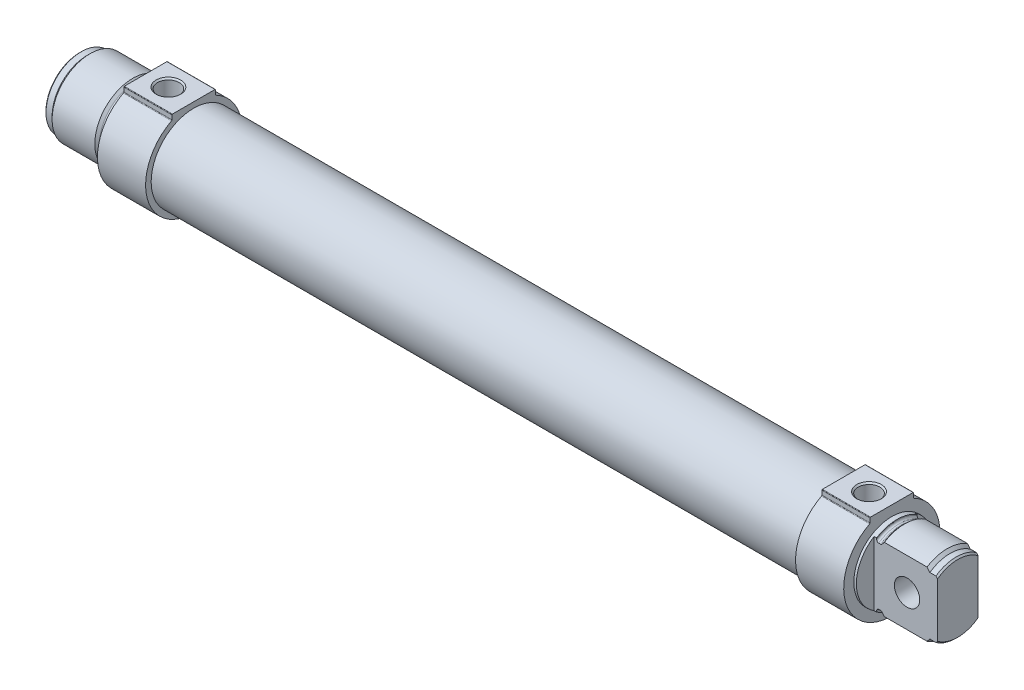
SolidWorks part; units mm, degrees
ref_plane "Front Plane" through (0, 0, 0) normal (0, 0, 1) x (1, 0, 0)
ref_plane "Top Plane" through (0, 0, 0) normal (0, 1, 0) x (1, 0, 0)
ref_plane "Right Plane" through (0, 0, 0) normal (1, 0, 0) x (0, 0, -1)
sketch "Sketch1" plane through (0, 0, 0) normal (0, 0, 1) x (1, 0, 0)
  line L0 (0, 0) -> (0, 13.3)
  line L1 (0, 13.3) -> (0.6, 13.9)
  line L2 (0.6, 13.9) -> (3, 13.9)
  line L3 (3, 13.9) -> (4.1, 15)
  line L4 (4.1, 15) -> (20.95, 15)
  line L5 (20.95, 15) -> (21.8657, 14.0843)
  line L6 (22.4314, 13.85) -> (23.2, 13.85)
  line L7 (24, 14.65) -> (24, 15)
  line L8 (24, 15) -> (26, 15)
  line L9 (26, 15) -> (26, 0)
  line L10 (26, 0) -> (0, 0)
  line L11 (26, 0) -> (0, 0) construction
  arc A0 (21.8657, 14.0843) -> (22.4314, 13.85) centre (22.4314, 14.65) ccw
  arc A1 (23.2, 13.85) -> (24, 14.65) centre (23.2, 14.65) ccw
revolve "Revolve1" add sketch "Sketch1" angle 360 about L11 reverse direction yes
cosmetic thread "Cosmetic Thread1" parameters "D1"=17.77, "D2"=28.16
ref_plane "Plane4" through (32, 0, 0) normal (1, 0, 0) x (0, 0, -1)
ref_plane "Plane5" through (16, 0, 0) normal (1, 0, 0) x (0, 0, -1)
ref_plane "Plane6" through (0, -20, 0) normal (0, 1, 0) x (1, 0, 0)
ref_plane "Plane7" through (0, 15, 0) normal (0, 1, 0) x (1, 0, 0)
ref_plane "Plane8" through (0, -9.5, 0) normal (0, 1, 0) x (1, 0, 0)
ref_plane "Plane9" through (0, 9.5, 0) normal (0, 1, 0) x (1, 0, 0)
ref_plane "Plane10" through (26, 0, 0) normal (1, 0, 0) x (0, 0, -1)
ref_plane "Plane11" through (26, 0, 0) normal (1, 0, 0) x (0, 0, -1)
ref_plane "Plane12" through (38.5, 0, 0) normal (1, 0, 0) x (0, 0, -1)
ref_plane "Plane13" through (31, 0, 0) normal (1, 0, 0) x (0, 0, -1)
ref_plane "Plane14" through (46, 0, 0) normal (1, 0, 0) x (0, 0, -1)
sketch "Sketch2" plane through (26, 0, 0) normal (1, 0, 0) x (0, 0, -1)
  line L0 (8.6, 17.1254) -> (8.6, 18.8)
  line L1 (8.4, 19) -> (-8.4, 19)
  line L2 (-8.6, 18.8) -> (-8.6, 17.1254)
  arc A0 (-8.7617, 16.8592) -> (8.7617, 16.8592) centre (0, 0) ccw
  arc A1 (8.7617, 16.8592) -> (8.6, 17.1254) centre (8.9, 17.1254) cw
  arc A2 (8.6, 18.8) -> (8.4, 19) centre (8.4, 18.8) ccw
  arc A3 (-8.4, 19) -> (-8.6, 18.8) centre (-8.4, 18.8) ccw
  arc A4 (-8.6, 17.1254) -> (-8.7617, 16.8592) centre (-8.9, 17.1254) cw
extrude "Boss-Extrude1" add sketch "Sketch2" along normal blind 19
ref_plane "Plane15" through (40.5, 0, 0) normal (1, 0, 0) x (0, 0, -1)
ref_plane "Plane16" through (0, 0, 0) normal (0, 0, 1) x (1, 0, 0)
ref_plane "Plane17" through (0, 0, -12.8) normal (0, 0, 1) x (1, 0, 0)
ref_plane "Plane18" through (0, 0, 0) normal (0, 1, 0) x (1, 0, 0)
ref_plane "Plane19" through (0, 9, 0) normal (0, 1, 0) x (1, 0, 0)
ref_plane "Plane20" through (0, 0, -6.6) normal (0, 0, 1) x (1, 0, 0)
ref_plane "Plane21" through (0, 0, 0) normal (0, 1, 0) x (1, 0, 0)
ref_plane "Plane22" through (0, 9, 0) normal (0, 1, 0) x (1, 0, 0)
ref_plane "Plane23" through (0, 9.8573, -1.7381) normal (0, 0.9848, -0.1736) x (1, 0, 0)
ref_plane "Plane24" through (0, 8.3801, -1.4776) normal (0, 0.9848, -0.1736) x (1, 0, 0)
sketch "Sketch3" plane through (0, 0, 0) normal (0, 0, 1) x (1, 0, 0)
  line L0 (45, 0) -> (45, 16.8)
  line L1 (45, 16.8) -> (301.5, 16.8)
  line L2 (301.5, 16.8) -> (301.5, 0)
  line L3 (301.5, 0) -> (45, 0)
  line L4 (301.5, 0) -> (45, 0) construction
revolve "Revolve2" add sketch "Sketch3" angle 360 about L4 reverse direction yes
ref_plane "Plane25" through (301.5, 0, 0) normal (1, 0, 0) x (0, 0, -1)
sketch "Sketch4" plane through (301.5, 0, 0) normal (1, 0, 0) x (0, 0, -1)
  line L0 (8.6, 17.1254) -> (8.6, 18.8)
  line L1 (8.4, 19) -> (-8.4, 19)
  line L2 (-8.6, 18.8) -> (-8.6, 17.1254)
  arc A0 (-8.7617, 16.8592) -> (8.7617, 16.8592) centre (0, 0) ccw
  arc A1 (8.7617, 16.8592) -> (8.6, 17.1254) centre (8.9, 17.1254) cw
  arc A2 (8.6, 18.8) -> (8.4, 19) centre (8.4, 18.8) ccw
  arc A3 (-8.4, 19) -> (-8.6, 18.8) centre (-8.4, 18.8) ccw
  arc A4 (-8.6, 17.1254) -> (-8.7617, 16.8592) centre (-8.9, 17.1254) cw
extrude "Boss-Extrude2" add sketch "Sketch4" along normal blind 19
ref_plane "Plane26" through (306, 0, 0) normal (1, 0, 0) x (0, 0, -1)
ref_plane "Plane27" through (306, 0, 0) normal (1, 0, 0) x (0, 0, -1)
ref_plane "Plane28" through (0, 0, 6.6) normal (0, 0, 1) x (1, 0, 0)
ref_plane "Plane29" through (0, 0, 0) normal (0, 1, 0) x (1, 0, 0)
ref_plane "Plane30" through (0, 9, 0) normal (0, 1, 0) x (1, 0, 0)
ref_plane "Plane31" through (0, 9.8573, 1.7381) normal (0, 0.9848, 0.1736) x (1, 0, 0)
ref_plane "Plane32" through (0, 8.3801, 1.4776) normal (0, 0.9848, 0.1736) x (1, 0, 0)
ref_plane "Plane33" through (375.5, 0, 0) normal (1, 0, 0) x (0, 0, -1)
ref_plane "Plane34" through (363, 0, 0) normal (1, 0, 0) x (0, 0, -1)
ref_plane "Plane35" through (370.5, 0, 0) normal (1, 0, 0) x (0, 0, -1)
ref_plane "Plane36" through (355.5, 0, 0) normal (1, 0, 0) x (0, 0, -1)
sketch "Sketch5" plane through (0, 0, 0) normal (0, 0, 1) x (1, 0, 0)
  line L0 (320.5, 0) -> (320.5, 15)
  line L1 (320.5, 15) -> (322.5, 15)
  line L2 (322.5, 15) -> (322.5, 14.65)
  line L3 (323.3, 13.85) -> (324.0686, 13.85)
  line L4 (324.6343, 14.0843) -> (325.55, 15)
  line L5 (325.55, 15) -> (342.4, 15)
  line L6 (342.4, 15) -> (343.5, 13.9)
  line L7 (343.5, 13.9) -> (345.9, 13.9)
  line L8 (345.9, 13.9) -> (346.5, 13.3)
  line L9 (346.5, 13.3) -> (346.5, 0)
  line L10 (346.5, 0) -> (320.5, 0)
  line L11 (346.5, 0) -> (320.5, 0) construction
  arc A0 (322.5, 14.65) -> (323.3, 13.85) centre (323.3, 14.65) ccw
  arc A1 (324.0686, 13.85) -> (324.6343, 14.0843) centre (324.0686, 14.65) ccw
revolve "Revolve3" add sketch "Sketch5" angle 360 about L11 reverse direction yes
cosmetic thread "Cosmetic Thread2" parameters "D1"=16.67, "D2"=28.16
sketch "Sketch6" plane through (0, 0, 0) normal (0, 1, 0) x (1, 0, 0)
  line L0 (321.5, 24) -> (321.5, 8)
  line L1 (321.5, 8) -> (346.5, 8)
  line L2 (346.5, 8) -> (346.5, -8)
  line L3 (346.5, -8) -> (321.5, -8)
  line L4 (321.5, -8) -> (321.5, -24)
  line L5 (321.5, -24) -> (362.5, -24)
  line L6 (362.5, -24) -> (362.5, 24)
  line L7 (362.5, 24) -> (321.5, 24)
extrude "Cut-Extrude1" cut sketch "Sketch6" along normal blind 19 and the other way blind 19
ref_plane "Plane37" through (334.5, 0, 0) normal (1, 0, 0) x (0, 0, -1)
sketch "Sketch7" plane through (334.5, 0, 0) normal (1, 0, 0) x (0, 0, -1)
  line L0 (-8, 0) -> (-8, 5)
  line L1 (-8, 5) -> (8, 5)
  line L2 (8, 5) -> (8, 0)
  line L3 (8, 0) -> (-8, 0)
  line L4 (8, 0) -> (-8, 0) construction
revolve "Cut-Revolve1" cut sketch "Sketch7" angle 360 about L4 reverse direction yes
hole_wizard "Hole1" positions "Sketch9" profile "Sketch8" legacy
sketch "Sketch9" plane through (0, 19, 0) normal (0, 1, 0) x (1, 0, 0)
  point P0 (35, 0)
sketch "Sketch8" plane through (35, 19, 0) normal (1, 0, 0) x (0, 0, 1)
  line L0 (0, 0) -> (0, 8.5)
  line L1 (0, 8.5) -> (4.283, 8.5)
  line L2 (4.283, 8.5) -> (4.283, 0.581)
  line L3 (4.283, 0.581) -> (4.864, 0)
  line L4 (4.864, 0) -> (0, 0)
  line L5 (0, -6.4453) -> (0, 115.525) construction
  line L6 (-4.283, 0.581) -> (-4.864, 0) construction
  dimension "Diameter" = 8.566
  dimension "Depth" = 8.5
  dimension "C-Sink Angle" = 90
  dimension "C-Sink Diameter" = 9.728
cosmetic thread "Cosmetic Thread3" parameters "D1"=7, "D2"=9.728
hole_wizard "Hole2" positions "Sketch11" profile "Sketch10" legacy
sketch "Sketch11" plane through (0, 19, 0) normal (0, 1, 0) x (1, 0, 0)
  point P0 (311.5, 0)
sketch "Sketch10" plane through (311.5, 19, 0) normal (1, 0, 0) x (0, 0, 1)
  line L0 (0, 0) -> (0, 8.5)
  line L1 (0, 8.5) -> (4.283, 8.5)
  line L2 (4.283, 8.5) -> (4.283, 0.581)
  line L3 (4.283, 0.581) -> (4.864, 0)
  line L4 (4.864, 0) -> (0, 0)
  line L5 (0, -6.4453) -> (0, 115.525) construction
  line L6 (-4.283, 0.581) -> (-4.864, 0) construction
  dimension "Diameter" = 8.566
  dimension "Depth" = 8.5
  dimension "C-Sink Angle" = 90
  dimension "C-Sink Diameter" = 9.728
cosmetic thread "Cosmetic Thread4" parameters "D1"=7, "D2"=9.728
sketch "Sketch12" plane through (0, 0, 0) normal (0, 0, 1) x (1, 0, 0)
  line L0 (-8, 0) -> (-8, 6)
  line L1 (-8, 6) -> (57, 6)
  line L2 (57, 6) -> (57, 16)
  line L3 (57, 16) -> (290, 16)
  line L4 (290, 16) -> (290, 0)
  line L5 (290, 0) -> (-8, 0)
  line L6 (290, 0) -> (-8, 0) construction
revolve "Cut-Revolve2" cut sketch "Sketch12" angle 360 about L6 reverse direction yes
ref_plane "Plane38" through (-8, 0, 0) normal (1, 0, 0) x (0, 0, -1)
ref_plane "Plane39" through (0, 19, 0) normal (0, 1, 0) x (1, 0, 0)
ref_plane "Plane40" through (8.5, 0, 0) normal (1, 0, 0) x (0, 0, -1)
ref_plane "Plane41" through (0, 0, 0) normal (1, 0, 0) x (0, 0, -1)
ref_plane "Plane42" through (26, 0, 0) normal (1, 0, 0) x (0, 0, -1)
ref_plane "Plane43" through (320.5, 0, 0) normal (1, 0, 0) x (0, 0, -1)
ref_plane "Plane44" through (26, 0, 0) normal (1, 0, 0) x (0, 0, -1)
ref_plane "Plane45" through (0, 19, 0) normal (0, 1, 0) x (1, 0, 0)
ref_plane "Plane46" through (54.5, 0, 0) normal (1, 0, 0) x (0, 0, -1)
ref_plane "Plane47" through (292, 0, 0) normal (1, 0, 0) x (0, 0, -1)
ref_plane "Plane48" through (0, 0, 0) normal (0, 0, 1) x (1, 0, 0)
ref_plane "Plane49" through (26, 0, 0) normal (1, 0, 0) x (0, 0, -1)
ref_plane "Plane50" through (0, 19, 0) normal (0, 1, 0) x (1, 0, 0)
ref_plane "FDT_FRONT XY" through (26, 0, 0) normal (1, 0, 0) x (0, 0, -1)
ref_plane "FDT_FRONT XZ" through (0, 0, 0) normal (0, -1, 0) x (-1, 0, 0)
ref_plane "FDT_FRONT YZ" through (0, 0, 0) normal (0, 0, -1) x (-1, 0, 0)
ref_axis "FDT_FRONT X" through (26, 0, 80.9) along (0, 0, -1)
ref_axis "FDT_FRONT Y" through (26, -50, 0) along (0, 1, 0)
ref_axis "FDT_FRONT Z" through (80.9, 0, 0) along (-1, 0, 0)
sketch3d "FDT_FRONT"
  point P0 (26, 0, 0)
ref_plane "FDT_QSFRONT XY" through (0, 19, 0) normal (0, 1, 0) x (1, 0, 0)
ref_plane "FDT_QSFRONT XZ" through (35, 0, 0) normal (-1, 0, 0) x (0, 0, 1)
ref_plane "FDT_QSFRONT YZ" through (0, 0, 0) normal (0, 0, 1) x (1, 0, 0)
ref_axis "FDT_QSFRONT X" through (35, 19, -50) along (0, 0, 1)
ref_axis "FDT_QSFRONT Y" through (-80.9, 19, 0) along (1, 0, 0)
ref_axis "FDT_QSFRONT Z" through (35, 50, 0) along (0, -1, 0)
sketch3d "FDT_QSFRONT"
  point P0 (35, 19, 0)
ref_plane "FDT_QSREAR XY" through (0, 19, 0) normal (0, 1, 0) x (1, 0, 0)
ref_plane "FDT_QSREAR XZ" through (311.5, 0, 0) normal (-1, 0, 0) x (0, 0, 1)
ref_plane "FDT_QSREAR YZ" through (0, 0, 0) normal (0, 0, 1) x (1, 0, 0)
ref_axis "FDT_QSREAR X" through (311.5, 19, -50) along (0, 0, 1)
ref_axis "FDT_QSREAR Y" through (-80.9, 19, 0) along (1, 0, 0)
ref_axis "FDT_QSREAR Z" through (311.5, 50, 0) along (0, -1, 0)
sketch3d "FDT_QSREAR"
  point P0 (311.5, 19, 0)
ref_plane "FDT_REAR XY" through (320.5, 0, 0) normal (-1, 0, 0) x (0, 0, 1)
ref_plane "FDT_REAR XZ" through (0, 0, 0) normal (0, 1, 0) x (1, 0, 0)
ref_plane "FDT_REAR YZ" through (0, 0, 0) normal (0, 0, -1) x (-1, 0, 0)
ref_axis "FDT_REAR X" through (320.5, 0, 80.9) along (0, 0, -1)
ref_axis "FDT_REAR Y" through (320.5, 50, 0) along (0, -1, 0)
ref_axis "FDT_REAR Z" through (-80.9, 0, 0) along (1, 0, 0)
sketch3d "FDT_REAR"
  point P0 (320.5, 0, 0)
ref_plane "FDT_SMBR1 XY" through (54.5, 0, 0) normal (-1, 0, 0) x (0, 0, 1)
ref_plane "FDT_SMBR1 XZ" through (0, 0, 0) normal (0, -1, 0) x (-1, 0, 0)
ref_plane "FDT_SMBR1 YZ" through (0, 0, 0) normal (0, 0, 1) x (1, 0, 0)
ref_axis "FDT_SMBR1 X" through (54.5, 0, -80.9) along (0, 0, 1)
ref_axis "FDT_SMBR1 Y" through (54.5, -50, 0) along (0, 1, 0)
ref_axis "FDT_SMBR1 Z" through (-80.9, 0, 0) along (1, 0, 0)
sketch3d "FDT_SMBR1"
  point P0 (54.5, 0, 0)
ref_plane "FDT_SMBR2 XY" through (292, 0, 0) normal (-1, 0, 0) x (0, 0, 1)
ref_plane "FDT_SMBR2 XZ" through (0, 0, 0) normal (0, -1, 0) x (-1, 0, 0)
ref_plane "FDT_SMBR2 YZ" through (0, 0, 0) normal (0, 0, 1) x (1, 0, 0)
ref_axis "FDT_SMBR2 X" through (292, 0, -80.9) along (0, 0, 1)
ref_axis "FDT_SMBR2 Y" through (292, -50, 0) along (0, 1, 0)
ref_axis "FDT_SMBR2 Z" through (-80.9, 0, 0) along (1, 0, 0)
sketch3d "FDT_SMBR2"
  point P0 (292, 0, 0)
ref_plane "FDT_SWIVELAXIS XY" through (0, 0, 0) normal (0, 0, 1) x (1, 0, 0)
ref_plane "FDT_SWIVELAXIS XZ" through (0, 0, 0) normal (0, -1, 0) x (-1, 0, 0)
ref_plane "FDT_SWIVELAXIS YZ" through (334.5, 0, 0) normal (1, 0, 0) x (0, 0, -1)
ref_axis "FDT_SWIVELAXIS X" through (-80.9, 0, 0) along (1, 0, 0)
ref_axis "FDT_SWIVELAXIS Y" through (334.5, -50, 0) along (0, 1, 0)
ref_axis "FDT_SWIVELAXIS Z" through (334.5, 0, 80.9) along (0, 0, -1)
sketch3d "FDT_SWIVELAXIS"
  point P0 (334.5, 0, 0)
ref_plane "NUT XY" through (8.5, 0, 0) normal (1, 0, 0) x (0, 0, -1)
ref_plane "NUT XZ" through (0, 0, 0) normal (0, -1, 0) x (-1, 0, 0)
ref_plane "NUT YZ" through (0, 0, 0) normal (0, 0, -1) x (-1, 0, 0)
ref_axis "NUT X" through (8.5, 0, 80.9) along (0, 0, -1)
ref_axis "NUT Y" through (8.5, -50, 0) along (0, 1, 0)
ref_axis "NUT Z" through (80.9, 0, 0) along (-1, 0, 0)
sketch3d "NUT"
  point P0 (8.5, 0, 0)
ref_plane "ZR XY" through (0, 0, 0) normal (1, 0, 0) x (0, 0, -1)
ref_plane "ZR XZ" through (0, 0, 0) normal (0, -1, 0) x (-1, 0, 0)
ref_plane "ZR YZ" through (0, 0, 0) normal (0, 0, -1) x (-1, 0, 0)
ref_axis "ZR X" through (0, 0, 80.9) along (0, 0, -1)
ref_axis "ZR Y" through (0, -50, 0) along (0, 1, 0)
ref_axis "ZR Z" through (80.9, 0, 0) along (-1, 0, 0)
sketch3d "ZR"
  point P0 (0, 0, 0)
ref_plane "ZYL XY" through (26, 0, 0) normal (1, 0, 0) x (0, 0, -1)
ref_plane "ZYL XZ" through (0, 0, 0) normal (0, -1, 0) x (-1, 0, 0)
ref_plane "ZYL YZ" through (0, 0, 0) normal (0, 0, -1) x (-1, 0, 0)
ref_axis "ZYL X" through (26, 0, 80.9) along (0, 0, -1)
ref_axis "ZYL Y" through (26, -50, 0) along (0, 1, 0)
ref_axis "ZYL Z" through (80.9, 0, 0) along (-1, 0, 0)
sketch3d "ZYL"
  point P0 (26, 0, 0)
sketch "Sketch13" plane through (0, 0, 0) normal (0, 0, 1) x (1, 0, 0)
  point P0 (334.5, 0)
